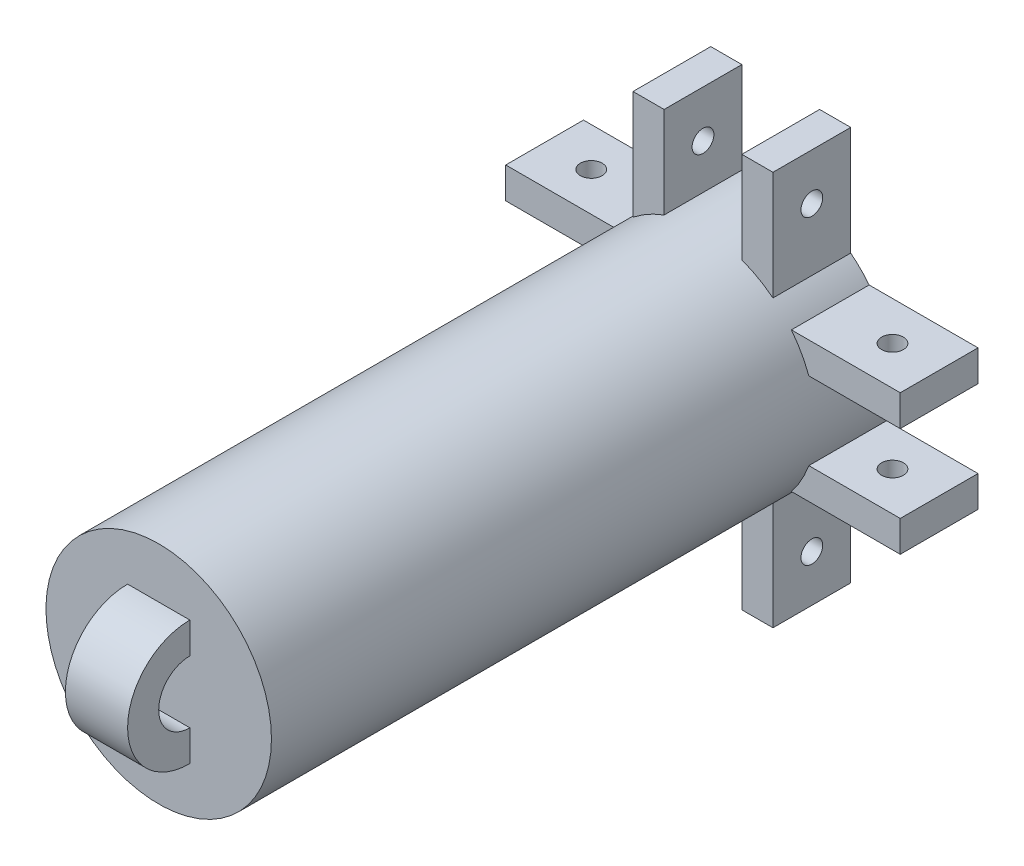
SolidWorks part; units mm, degrees
ref_plane "Front Plane" through (0, 0, 0) normal (0, 0, 1) x (1, 0, 0)
ref_plane "Top Plane" through (0, 0, 0) normal (0, 1, 0) x (1, 0, 0)
ref_plane "Right Plane" through (0, 0, 0) normal (1, 0, 0) x (0, 0, -1)
sketch "Sketch1" plane through (0, 0, 0) normal (0, 0, 1) x (1, 0, 0)
  circle A0 centre (0, 0) radius 18.415
  dimension "D1" = 36.83
extrude "Boss-Extrude1" add sketch "Sketch1" along normal blind 101.6
sketch "Sketch8" plane through (0, 0, 0) normal (0, 0, 1) x (1, 0, 0)
  line L0 (-14.4384, 11.43) -> (-32.2184, 11.43)
  line L1 (-32.2184, 11.43) -> (-32.2184, -11.43)
  line L2 (-32.2184, -11.43) -> (-14.4384, -11.43)
  arc A0 (-14.4384, 11.43) -> (-14.4384, -11.43) centre (0, 0) ccw
  circle A1 centre (0, 0) radius 18.415 construction
  dimension "D1" = 22.86
  dimension "D2" = 17.78
  dimension "D3" = 17.78
extrude "Boss-Extrude4" add sketch "Sketch8" along normal blind 12.7
sketch "Sketch9" plane through (0, -11.43, 0) normal (0, -1, 0) x (1, 0, 0)
  line L1 (-32.2184, 12.7) -> (-32.2184, 0) construction
  circle A0 centre (-24.5984, 6.35) radius 1.778
  point P7 (-32.2184, 6.35)
  dimension "D1" = 3.556
  dimension "D2" = 7.62
extrude "Cut-Extrude2" cut sketch "Sketch9" against normal blind 25.4
sketch "Sketch13" plane through (0, 0, 0) normal (1, 0, 0) x (0, 0, -1)
  line L0 (-101.6, 10.16) -> (-101.6, -10.16)
  line L1 (-101.6, 18.415) -> (-101.6, -18.415) construction
  arc A0 (-101.6, -10.16) -> (-101.6, 10.16) centre (-101.6, 0) cw
  point P5 (-88.9, -4.3687)
  dimension "D1" = 10.16
extrude "Boss-Extrude5" add sketch "Sketch13" along normal blind 5.08 and the other way blind 5.08
sketch "Sketch14" plane through (5.08, 0, 0) normal (1, 0, 0) x (0, 0, -1)
  line L0 (-101.6, 5.08) -> (-101.6, -5.08)
  line L1 (-101.6, -10.16) -> (-101.6, 10.16) construction
  arc A0 (-101.6, 5.08) -> (-101.6, -5.08) centre (-101.6, 0) ccw
  arc A1 (-101.6, 10.16) -> (-101.6, -10.16) centre (-101.6, 0) ccw construction
  dimension "D1" = 5.08
extrude "Cut-Extrude3" cut sketch "Sketch14" against normal blind 15.24
sketch "Sketch15" plane through (0, 0, 12.7) normal (0, 0, 1) x (1, 0, 0)
  line L0 (-17.2855, 6.35) -> (-32.2184, 6.35)
  line L1 (-32.2184, 11.43) -> (-32.2184, -11.43) construction
  line L2 (-32.2184, 6.35) -> (-32.2184, -6.35)
  line L3 (-32.2184, -6.35) -> (-17.2855, -6.35)
  arc A0 (-17.2855, 6.35) -> (-17.2855, -6.35) centre (0, 0) ccw
  arc A1 (-14.4384, 11.43) -> (-14.4384, -11.43) centre (0, 0) ccw construction
  point P7 (-32.2184, 0)
  dimension "D1" = 12.7
extrude "Cut-Extrude4" cut sketch "Sketch15" against normal blind 12.7
pattern_circular "CirPattern1" count 4 over 360 about axis through (0, 0, 101.6) along (0, 0, -1) of "Boss-Extrude4", "Cut-Extrude2", "Cut-Extrude4" reverse direction yes
